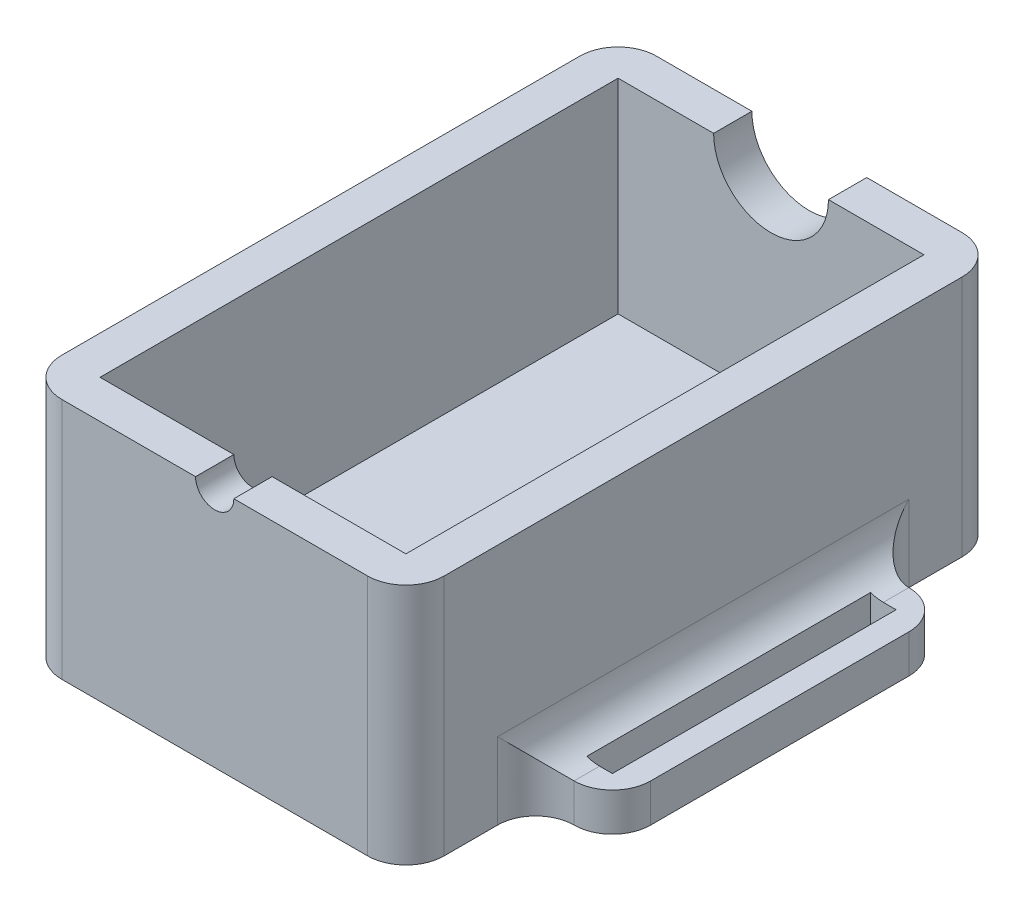
SolidWorks part; units mm, degrees
ref_plane "Front Plane" through (0, 0, 0) normal (0, 0, 1) x (1, 0, 0)
ref_plane "Top Plane" through (0, 0, 0) normal (0, 1, 0) x (1, 0, 0)
ref_plane "Right Plane" through (0, 0, 0) normal (1, 0, 0) x (0, 0, -1)
sketch "Sketch1" plane through (0, 0, 0) normal (0, 1, 0) x (1, 0, 0)
  line L0 (-11.985, 20.3) -> (-11.985, -20.3) construction
  line L1 (-11.685, 20) -> (11.685, 20) construction
  line L2 (-11.685, 20) -> (-11.685, -20) construction
  line L3 (-11.685, -20) -> (11.685, -20) construction
  line L4 (11.685, 20) -> (11.685, -20) construction
  line L5 (-11.685, 20) -> (11.685, -20) construction
  line L6 (-11.685, -20) -> (11.685, 20) construction
  line L7 (-11.985, -20.3) -> (11.985, -20.3) construction
  line L8 (11.985, 20.3) -> (11.985, -20.3) construction
  line L9 (-11.985, 20.3) -> (11.985, 20.3) construction
  line L10 (-14.985, 23.3) -> (-14.985, -23.3)
  line L11 (-14.985, -23.3) -> (14.985, -23.3)
  line L12 (14.985, 23.3) -> (14.985, -23.3)
  line L13 (-14.985, 23.3) -> (14.985, 23.3)
  point P0 (0, 0)
  dimension "D1" = 40
  dimension "D2" = 23.37
  dimension "D3" = 0.3
  dimension "D4" = 3
extrude "Boss-Extrude1" add sketch "Sketch1" along normal blind 3
sketch "Sketch2" plane through (0, 3, 0) normal (0, 1, 0) x (1, 0, 0)
  line L8 (11.985, 20.3) -> (-11.985, 20.3)
  line L9 (-11.985, 20.3) -> (-11.985, -20.3)
  line L10 (-11.985, -20.3) -> (11.985, -20.3)
  line L11 (11.985, -20.3) -> (11.985, 20.3)
  line L12 (11.985, 20.3) -> (-11.985, 20.3)
  line L13 (-11.985, 20.3) -> (-11.985, -20.3)
  line L14 (-11.985, -20.3) -> (11.985, -20.3)
  line L15 (11.985, -20.3) -> (11.985, 20.3)
  line L16 (14.985, 23.3) -> (-14.985, 23.3)
  line L17 (-14.985, 23.3) -> (-14.985, -23.3)
  line L18 (-14.985, -23.3) -> (14.985, -23.3)
  line L19 (14.985, -23.3) -> (14.985, 23.3)
  line L20 (14.985, 23.3) -> (-14.985, 23.3)
  line L21 (-14.985, 23.3) -> (-14.985, -23.3)
  line L22 (-14.985, -23.3) -> (14.985, -23.3)
  line L23 (14.985, -23.3) -> (14.985, 23.3)
  dimension "D1" = 3
  dimension "D2" = 0
extrude "Boss-Extrude2" add sketch "Sketch2" along normal blind 16
sketch "Sketch3" plane through (0, 0, -23.3) normal (0, 0, -1) x (-1, 0, 0)
  line L0 (0, 19) -> (0, 0) construction
  line L1 (-14.985, 19) -> (14.985, 19) construction
  line L2 (-14.985, 0) -> (14.985, 0) construction
  line L3 (4.5, 19) -> (-4.5, 19)
  arc A0 (-4.5, 19) -> (4.5, 19) centre (0, 19) ccw
  dimension "D1" = 4.5
extrude "Cut-Extrude1" cut sketch "Sketch3" against normal up to surface (3 mm away) up to face at (0, 11, -20.3)
sketch "Sketch4" plane through (0, 0, 23.3) normal (0, 0, 1) x (1, 0, 0)
  line L0 (0, 19) -> (0, 0) construction
  line L1 (-14.985, 19) -> (14.985, 19) construction
  line L2 (-14.985, 0) -> (14.985, 0) construction
  line L3 (1.5, 19) -> (-1.5, 19)
  arc A0 (-1.5, 19) -> (1.5, 19) centre (0, 19) ccw
  dimension "D1" = 1.5
extrude "Cut-Extrude2" cut sketch "Sketch4" against normal up to surface (3 mm away) up to face at (0, 11, 20.3)
fillet "Fillet1" radius 3 4 edges at (-14.985, 9.5, -23.3) (-14.985, 9.5, 23.3) (14.985, 9.5, 23.3) (14.985, 9.5, -23.3)
sketch "Sketch5" plane through (0, 0, 0) normal (0, -1, 0) x (1, 0, 0)
  line L0 (-14.985, -20.3) -> (-14.985, 20.3) construction
  line L1 (-14.985, 13.1179) -> (-20.985, 13.1179)
  line L2 (-14.985, 13.1179) -> (-14.985, -13.1179)
  line L3 (-14.985, -13.1179) -> (-20.985, -13.1179)
  line L4 (-20.985, 13.1179) -> (-20.985, -13.1179)
  line L5 (14.985, 20.3) -> (14.985, -20.3) construction
  line L6 (14.985, -13.1179) -> (20.985, -13.1179)
  line L7 (14.985, -13.1179) -> (14.985, 13.1179)
  line L8 (14.985, 13.1179) -> (20.985, 13.1179)
  line L9 (20.985, -13.1179) -> (20.985, 13.1179)
  line L10 (-14.985, 0) -> (-26.468, 0) construction
  point P14 (0, 0)
  dimension "D1" = 6
extrude "Boss-Extrude3" add sketch "Sketch5" against normal blind 3
sketch "Sketch6" plane through (0, 3, 0) normal (0, 1, 0) x (1, 0, 0)
  line L12 (-16.985, -11.1179) -> (-16.985, 11.1179)
  line L13 (-16.985, 11.1179) -> (-18.985, 11.1179)
  line L14 (-18.985, 11.1179) -> (-18.985, -11.1179)
  line L15 (-18.985, -11.1179) -> (-16.985, -11.1179)
  line L16 (-16.985, -11.1179) -> (-16.985, 11.1179)
  line L17 (-16.985, 11.1179) -> (-18.985, 11.1179)
  line L18 (-18.985, 11.1179) -> (-18.985, -11.1179)
  line L19 (-18.985, -11.1179) -> (-16.985, -11.1179)
  line L24 (16.985, 11.1179) -> (16.985, -11.1179)
  line L25 (16.985, -11.1179) -> (18.985, -11.1179)
  line L26 (18.985, -11.1179) -> (18.985, 11.1179)
  line L27 (18.985, 11.1179) -> (16.985, 11.1179)
  line L28 (16.985, 11.1179) -> (16.985, -11.1179)
  line L29 (16.985, -11.1179) -> (18.985, -11.1179)
  line L30 (18.985, -11.1179) -> (18.985, 11.1179)
  line L31 (18.985, 11.1179) -> (16.985, 11.1179)
  dimension "D1" = 2
  dimension "D2" = 2
extrude "Cut-Extrude3" cut sketch "Sketch6" against normal through all
fillet "Fillet2" radius 3 10 edges at (-20.985, 1.5, -13.1179) (-20.985, 1.5, 13.1179) (20.985, 1.5, -13.1179) (20.985, 1.5, 13.1179) (14.985, 1.5, 13.1179) (14.985, 3, 0) (14.985, 1.5, -13.1179) (-14.985, 3, 0) (-14.985, 1.5, -13.1179) (-14.985, 1.5, 13.1179)
